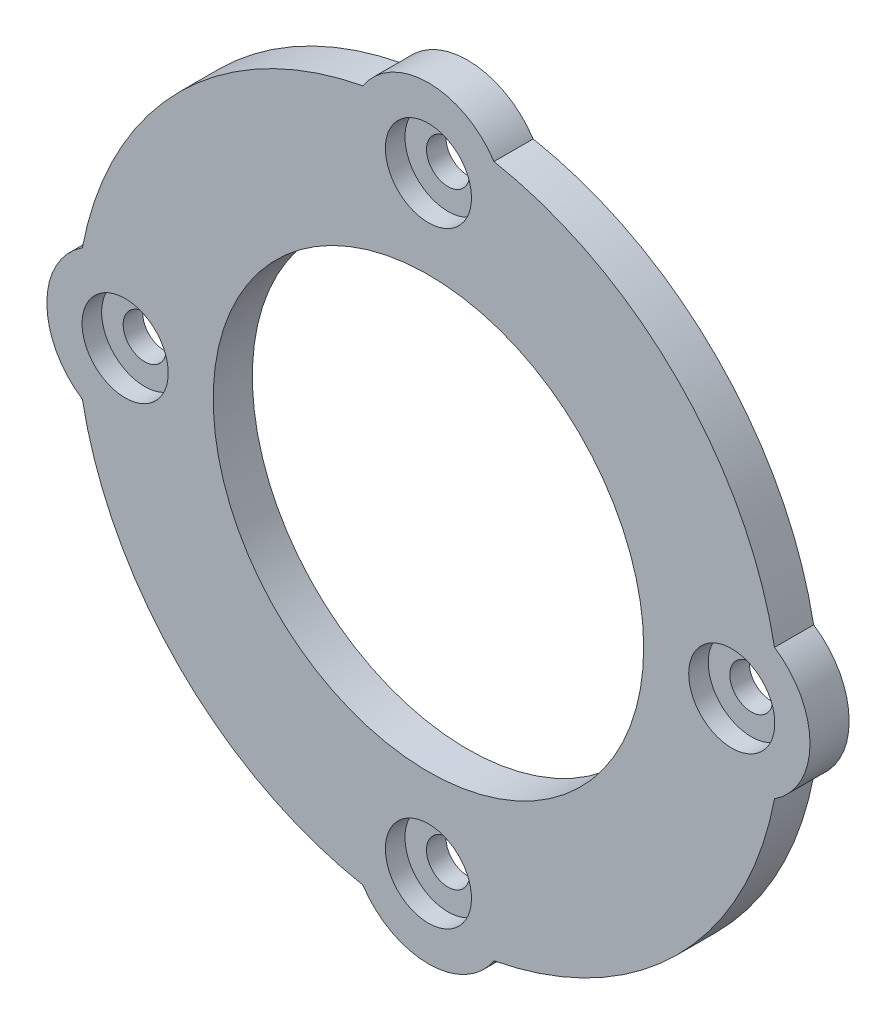
SolidWorks part; units mm, degrees
material "ABS"
ref_plane "Спереди" through (0, 0, 0) normal (0, 0, 1) x (1, 0, 0)
ref_plane "Сверху" through (0, 0, 0) normal (0, 1, 0) x (1, 0, 0)
ref_plane "Справа" through (0, 0, 0) normal (1, 0, 0) x (0, 0, -1)
sketch "Эскиз1" plane through (0, 0, 0) normal (0, 0, 1) x (1, 0, 0)
  arc A0 (-17.6855, -3.3502) -> (-3.3502, -17.6855) centre (0, 0) ccw
  circle A1 centre (0, 0) radius 15.5 construction
  arc A2 (-17.6855, 3.3502) -> (-17.6855, -3.3502) centre (-15.5, 0) ccw
  arc A3 (3.3502, 17.6855) -> (-3.3502, 17.6855) centre (0, 15.5) ccw
  arc A4 (17.6855, -3.3502) -> (17.6855, 3.3502) centre (15.5, 0) ccw
  arc A5 (-3.3502, -17.6855) -> (3.3502, -17.6855) centre (0, -15.5) ccw
  arc A6 (-3.3502, 17.6855) -> (-17.6855, 3.3502) centre (0, 0) ccw
  arc A7 (17.6855, 3.3502) -> (3.3502, 17.6855) centre (0, 0) ccw
  arc A8 (3.3502, -17.6855) -> (17.6855, -3.3502) centre (0, 0) ccw
  point P18 (0, 0)
  dimension "D1" = 36
  dimension "D2" = 31
  dimension "D3" = 8
extrude "Бобышка-Вытянуть1" add sketch "Эскиз1" along normal blind 2
sketch "Эскиз2" plane through (0, 0, 2) normal (0, 0, 1) x (1, 0, 0)
  circle A0 centre (0, 0) radius 11
  dimension "D1" = 22
extrude "Вырез-Вытянуть1" cut sketch "Эскиз2" against normal through all
sketch "Эскиз3" plane through (0, 0, 2) normal (0, 0, 1) x (1, 0, 0)
  circle A0 centre (-15.5, 0) radius 2.2
  point P12 (0, 0)
  dimension "D1" = 4.4
  dimension "D2" = 15.5
extrude "Вырез-Вытянуть2" cut sketch "Эскиз3" against normal blind 1 contours A0
sketch "Эскиз4" plane through (0, 0, 1) normal (0, 0, 1) x (1, 0, 0)
  circle A0 centre (-15.5, 0) radius 1.1
  dimension "D1" = 2.2
extrude "Вырез-Вытянуть3" cut sketch "Эскиз4" against normal through all
pattern_circular "Круговой массив1" count 4 over 360 about axis through (0, 0, 2) along (0, 0, -1) of "Вырез-Вытянуть2", "Вырез-Вытянуть3"
